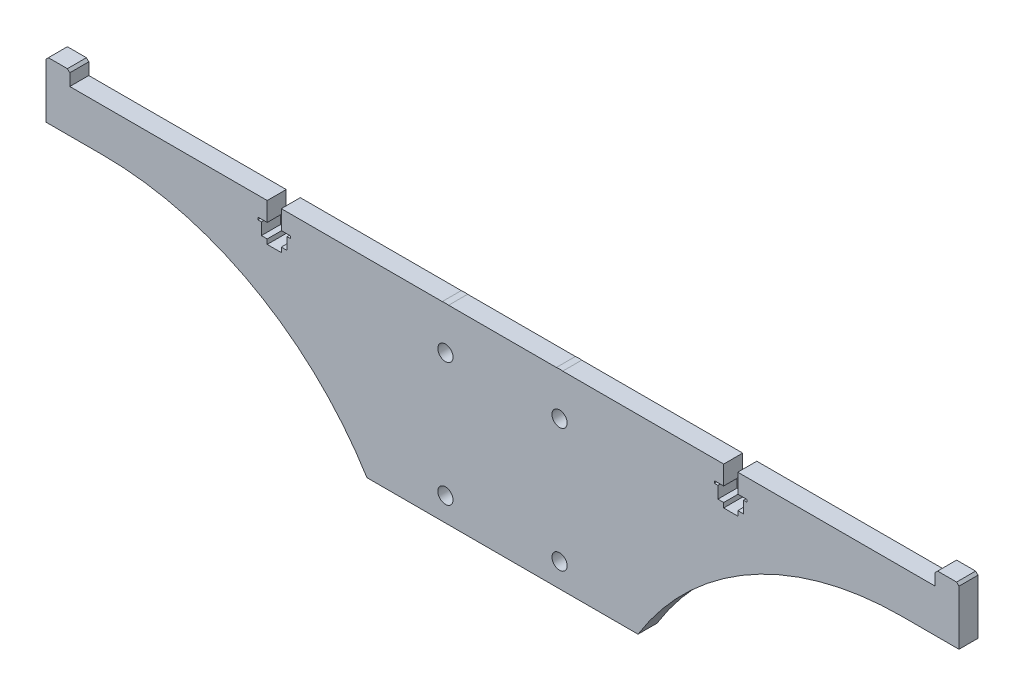
SolidWorks part; units mm, degrees
material "Oak"
ref_plane "Front Plane" through (0, 0, 0) normal (0, 0, 1) x (1, 0, 0)
ref_plane "Top Plane" through (0, 0, 0) normal (0, 1, 0) x (1, 0, 0)
ref_plane "Right Plane" through (0, 0, 0) normal (1, 0, 0) x (0, 0, -1)
sketch "Sketch1" plane through (0, 0, 0) normal (0, 0, 1) x (1, 0, 0)
  line L0 (0, -43.0686) -> (0, 56.6488) construction
  line L1 (0, 22) -> (-11.3303, 22)
  line L2 (-28.5, 10.5) -> (28.5, 10.5) construction
  line L3 (-28.5, 10.5) -> (-28.5, -10.5) construction
  line L4 (-28.5, -10.5) -> (28.5, -10.5) construction
  line L5 (28.5, 10.5) -> (28.5, -10.5) construction
  line L6 (91, 22) -> (91, 25)
  line L7 (91, 25) -> (96, 25)
  line L8 (96, 25) -> (96, 13)
  line L9 (28.5, -10.5) -> (28.5, -18) construction
  line L10 (28.5, -18) -> (0, -18)
  line L11 (-28.5, 10.5) -> (28.5, -10.5) construction
  line L12 (28.5, 10.5) -> (-28.5, -10.5) construction
  line L13 (-96, 25) -> (-96, 13)
  line L14 (96, 13) -> (84, 13)
  line L15 (-96, 13) -> (-84, 13)
  line L21 (-91, 25) -> (-96, 25)
  line L22 (-91, 22) -> (-91, 25)
  line L25 (0, 22) -> (11.3303, 22)
  line L26 (-12.6697, 22) -> (-91, 22)
  line L32 (12.6697, 22) -> (91, 22)
  line L33 (0, -18) -> (-28.5, -18)
  arc A0 (-11.3303, 22) -> (-12.6697, 22) centre (-12, 17.5501) ccw
  arc A1 (12.6697, 22) -> (11.3303, 22) centre (12, 17.5501) ccw
  arc A2 (-84, 13) -> (-28.5, -18) centre (-84, -52.1815) cw
  arc A4 (84, 13) -> (28.5, -18) centre (84, -52.1815) ccw
  point P9 (0, 0)
  point P20 (0, 0)
  point P24 (0, 40)
  point P27 (73.331, 42)
  point P30 (0, 40)
  point P31 (68.331, 22)
  point P32 (99.8, 42)
  point P38 (98.8347, 49.7973)
  point P52 (0, -4.5)
  point P54 (0, 7)
  dimension "D8" = 4.5
  dimension "D1" = 57
  dimension "D2" = 22
  dimension "D3" = 96
  dimension "D4" = 5
  dimension "D5" = 21
  dimension "D6" = 12
  dimension "D7" = 12
  dimension "D10" = 3
  dimension "D11" = 12
  dimension "D9" = 9
  dimension "D16" = 40
extrude "Boss-Extrude1" add sketch "Sketch1" along normal blind 4
sketch "Sketch2" plane through (0, 0, 4) normal (0, 0, 1) x (1, 0, 0)
  line L0 (0, 0) -> (0, -18) construction
  line L5 (-28.5, -18) -> (28.5, -18) construction
  line L7 (4, -6) -> (4, 10) construction
  line L8 (4, -6) -> (20, -6) construction
  line L9 (4, 10) -> (20, 10) construction
  line L10 (20, -6) -> (20, 10) construction
  line L11 (4, -6) -> (20, 10) construction
  line L12 (4, 10) -> (20, -6) construction
  line L13 (11.3303, 22) -> (-11.3303, 22) construction
  circle A0 centre (12, -13) radius 1.6
  circle A1 centre (12, 13) radius 1.6
  point P7 (12, 2)
  dimension "D2" = 3.2
  dimension "D1" = 12
  dimension "D4" = 15
  dimension "D6" = 20
  dimension "D7" = 16
  dimension "D16" = 11
extrude "Cut-Extrude1" cut sketch "Sketch2" against normal through all
mirror "Mirror1" about plane through (0, 0, 0) normal (1, 0, 0) of "Cut-Extrude1"
chamfer "Chamfer1" distance 0.5 angle 45 4 edges at (96, 25, 2) (91, 25, 2) (-91, 25, 2) (-96, 25, 2)
sketch "Sketch4" plane through (0, 0, 4) normal (0, 0, 1) x (1, 0, 0)
  line L0 (0, 0) -> (0, 22.5154) construction
  line L1 (-48, 22) -> (-48, 14) construction
  line L2 (11.3303, 22) -> (-11.3303, 22) construction
  line L3 (-49.48, 22) -> (-49.48, 18)
  line L4 (-49.48, 18) -> (-51.45, 18)
  line L5 (-51.45, 18) -> (-51.45, 17.5)
  line L6 (-51.45, 17.5) -> (-50.7, 17.5)
  line L7 (-50.7, 17.5) -> (-50.7, 15)
  line L8 (-50.7, 15) -> (-49.48, 15)
  line L9 (-49.48, 15) -> (-49.48, 14)
  line L10 (-49.48, 14) -> (-46.52, 14)
  line L11 (-46.52, 15) -> (-46.52, 14)
  line L12 (-45.3, 15) -> (-46.52, 15)
  line L13 (-45.3, 17.5) -> (-45.3, 15)
  line L14 (-44.55, 17.5) -> (-45.3, 17.5)
  line L15 (-44.55, 18) -> (-44.55, 17.5)
  line L16 (-46.52, 18) -> (-44.55, 18)
  line L17 (-46.52, 22) -> (-46.52, 18)
  line L18 (48, 22) -> (48, 14) construction
  line L19 (46.52, 22) -> (46.52, 18)
  line L20 (46.52, 18) -> (44.55, 18)
  line L21 (44.55, 18) -> (44.55, 17.5)
  line L22 (44.55, 17.5) -> (45.3, 17.5)
  line L23 (45.3, 17.5) -> (45.3, 15)
  line L24 (45.3, 15) -> (46.52, 15)
  line L25 (46.52, 15) -> (46.52, 14)
  line L26 (49.48, 14) -> (46.52, 14)
  line L27 (49.48, 15) -> (49.48, 14)
  line L28 (50.7, 15) -> (49.48, 15)
  line L29 (50.7, 17.5) -> (50.7, 15)
  line L30 (51.45, 17.5) -> (50.7, 17.5)
  line L31 (51.45, 18) -> (51.45, 17.5)
  line L32 (49.48, 18) -> (51.45, 18)
  line L33 (49.48, 22) -> (49.48, 18)
  line L34 (-49.48, 22) -> (-46.52, 22)
  line L35 (46.52, 22) -> (49.48, 22)
  dimension "D1" = 0.5
  dimension "D2" = 2.5
  dimension "D3" = 1
  dimension "D4" = 8
  dimension "D5" = 2.96
  dimension "D6" = 6.9
  dimension "D7" = 5.4
  dimension "D8" = 48
extrude "Cut-Extrude2" cut sketch "Sketch4" against normal through all
equation "\"bed-plate-thickness\"=3"
equation "\"D1@Boss-Extrude1\"=\"y-cross-rib-thickness\""
equation "\"D10@Sketch1\"=\"bed-plate-thickness\""
equation "\"y-cross-rib-thickness\"=4"
equation "\"y-rib-thickness\"=6"
equation "\"x-plate-thickness\"=5"
equation "\"rod-diameter\"=12"
equation "\"t-nut-hole-diameter\"=3"
equation "\"D7@Sketch1\" = \"D6@Sketch1\""
